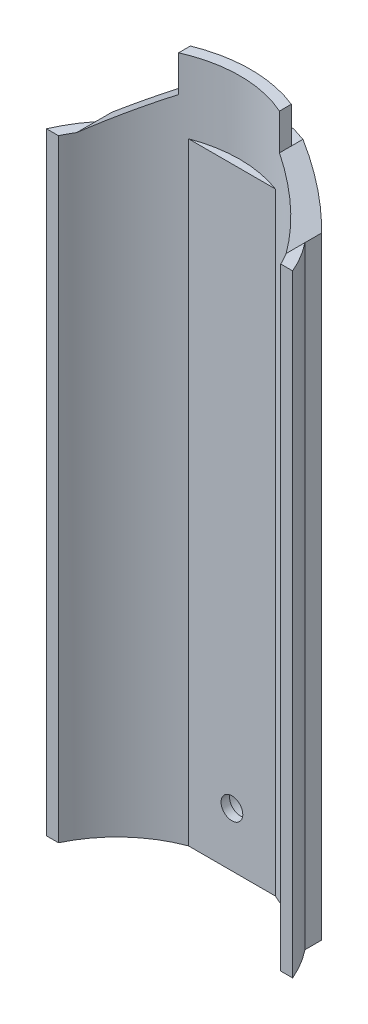
SolidWorks part; units mm, degrees
material "尼龙 6/10"
ref_plane "前视基准面" through (0, 0, 0) normal (0, 0, 1) x (1, 0, 0)
ref_plane "上视基准面" through (0, 0, 0) normal (0, 1, 0) x (1, 0, 0)
ref_plane "右视基准面" through (0, 0, 0) normal (1, 0, 0) x (0, 0, -1)
other "Configuration Table"
sketch "草图1" plane through (0, 0, 0) normal (0, 1, 0) x (1, 0, 0)
  circle A0 centre (0, 0) radius 20
  circle A1 centre (0, 0) radius 17
  dimension "D1" = 40
  dimension "D2" = 34
extrude "凸台-拉伸1" add sketch "草图1" along normal blind 80.6
sketch "草图2" plane through (0, 0, 0) normal (0, 0, 1) x (1, 0, 0)
  line L0 (-14.47, 0) -> (14.47, 0) construction
  line L1 (-20, 0) -> (20, 0) construction
  line L3 (-14.47, 0) -> (-20, 0)
  line L4 (-14.47, 0) -> (-14.47, 80.6)
  line L5 (-14.47, 80.6) -> (-20, 80.6)
  line L6 (-20, 0) -> (-20, 80.6)
  line L7 (14.47, 0) -> (20, 0)
  line L8 (14.47, 0) -> (14.47, 80.6)
  line L9 (14.47, 80.6) -> (20, 80.6)
  line L10 (20, 0) -> (20, 80.6)
  point P6 (0, 0)
  dimension "D1" = 28.94
extrude "切除-拉伸1" cut sketch "草图2" against normal through all
sketch "草图3" plane through (0, 0, 0) normal (0, 0, 1) x (1, 0, 0)
  line L0 (-6.97, 80.6) -> (6.97, 80.6) construction
  line L1 (14.47, 80.6) -> (-14.47, 80.6) construction
  line L3 (-6.97, 80.6) -> (-14.47, 75.6)
  line L8 (-14.47, 0) -> (-14.47, 80.6) construction
  line L10 (6.97, 80.6) -> (14.47, 75.6)
  line L11 (14.47, 80.6) -> (14.47, 0) construction
  line L12 (14.47, 75.6) -> (14.47, 80.6)
  line L13 (14.47, 80.6) -> (6.97, 80.6)
  line L14 (-14.47, 75.6) -> (-14.47, 80.6)
  line L15 (-14.47, 80.6) -> (-6.97, 80.6)
  point P5 (0, 80.6)
  dimension "D1" = 13.94
  dimension "D2" = 5
  dimension "D3" = 7.5
  dimension "D4" = 5
extrude "切除-拉伸2" cut sketch "草图3" against normal through all
sketch "草图4" plane through (0, 0, 0) normal (0, 1, 0) x (1, 0, 0)
  line L0 (0, -1000) -> (0, 49000) construction
  line L1 (-17, 7.2973) -> (-15.3542, 7.2973)
  line L2 (15.3542, 7.2973) -> (17, 7.2973)
  arc A0 (15.3542, 7.2973) -> (-15.3542, 7.2973) centre (0, 0) ccw
  arc A1 (17, 7.2973) -> (-17, 7.2973) centre (0, 0) ccw
  point P9 (0, 7.2973)
  dimension "D1" = 34
  dimension "D2" = 37
  dimension "D3" = 34
extrude "凸台-拉伸3" add sketch "草图4" along normal blind 75.6
sketch "草图5" plane through (0, 0, 0) normal (0, 1, 0) x (1, 0, 0)
  line L0 (0, -1000) -> (0, 49000) construction
  line L1 (-6.97, 17.1368) -> (6.97, 17.1368) construction
  line L2 (6.97, 17.1368) -> (6.97, 15.5055)
  line L3 (-6.97, 17.1368) -> (-6.97, 15.5055)
  arc A0 (6.97, 17.1368) -> (-6.97, 17.1368) centre (0, 0) ccw
  arc A2 (6.97, 15.5055) -> (-6.97, 15.5055) centre (0, 0) ccw
  point P11 (0, 17.1368)
  dimension "D1" = 13.94
extrude "凸台-拉伸5" add sketch "草图5" along normal blind 5 from surface starting at face at (0, 80.6, -17.8129)
sketch "草图6" plane through (0, 0, 0) normal (0, 1, 0) x (1, 0, 0)
  line L4 (14.47, 11.5269) -> (14.47, 13.8065)
  line L5 (15.3542, 7.2973) -> (17, 7.2973)
  line L6 (-17, 7.2973) -> (-15.3542, 7.2973)
  line L7 (-14.47, 13.8065) -> (-14.47, 11.5269)
  line L8 (14.47, 11.5269) -> (14.47, 13.8065)
  line L9 (15.3542, 7.2973) -> (17, 7.2973)
  line L10 (-17, 7.2973) -> (-15.3542, 7.2973)
  line L11 (-14.47, 13.8065) -> (-14.47, 11.5269)
  arc A4 (17, 7.2973) -> (14.47, 11.5269) centre (0, 0) ccw
  arc A5 (15.3542, 7.2973) -> (-15.3542, 7.2973) centre (0, 0) ccw
  arc A6 (-14.47, 11.5269) -> (-17, 7.2973) centre (0, 0) ccw
  arc A7 (14.47, 13.8065) -> (-14.47, 13.8065) centre (0, 0) ccw
  arc A8 (17, 7.2973) -> (14.47, 11.5269) centre (0, 0) ccw
  arc A9 (15.3542, 7.2973) -> (-15.3542, 7.2973) centre (0, 0) ccw
  arc A10 (-14.47, 11.5269) -> (-17, 7.2973) centre (0, 0) ccw
  arc A11 (14.47, 13.8065) -> (-14.47, 13.8065) centre (0, 0) ccw
  dimension "D1" = 0
extrude "凸台-拉伸6" add sketch "草图6" against normal blind 9
sketch "草图7" plane through (0, 0, 0) normal (0, 1, 0) x (1, 0, 0)
  line L0 (0, -1000) -> (0, 49000) construction
  line L1 (-6, 15.906) -> (6, 15.906)
  arc A0 (6, 15.906) -> (-6, 15.906) centre (0, 0) ccw
  point P9 (0, 15.906)
  dimension "D1" = 12
extrude "凸台-拉伸7" add sketch "草图7" along normal up to vertex (75.6 mm away) from surface up to point (-14.47, 75.6, -8.923) starting at face at (0, -9, -11.9902)
sketch "草图8" plane through (0, 0, 0) normal (0, 1, 0) x (1, 0, 0)
  line L0 (6, 15.906) -> (6, 19.0788) construction
  line L1 (6, 19.0788) -> (-6, 19.0788)
  line L2 (-6, 19.0788) -> (-6, 15.906) construction
  arc A0 (14.47, 13.8065) -> (-14.47, 13.8065) centre (0, 0) ccw construction
  arc A1 (6, 19.0788) -> (-6, 19.0788) centre (0, 0) ccw
extrude "切除-拉伸3" cut sketch "草图8" along normal blind 15 from surface starting at face at (0, -9, -11.9845)
sketch "草图9" plane through (0, 0, 0) normal (0, 0, 1) x (1, 0, 0)
  line L0 (-6, -9) -> (6, -9) construction
  line L1 (-6, 6) -> (-6, -9) construction
  circle A0 centre (0, -1.5) radius 1.5
  dimension "D1" = 3
  dimension "D2" = 7.5
  dimension "D3" = 6
extrude "切除-拉伸4" cut sketch "草图9" against normal through all
sketch "草图10" plane through (0, 0, 0) normal (0, 0, 1) x (1, 0, 0)
  circle A0 centre (0, -1.5) radius 2.6
  dimension "D1" = 5.2
extrude "切除-拉伸5" cut sketch "草图10" along normal blind 2 from surface starting at face at (-1.5, -1.5, -19.0788)
sketch "草图11" plane through (0, 0, 0) normal (0, 0, 1) x (1, 0, 0)
  line L0 (6, 6) -> (2, 6)
  line L1 (-6, 6) -> (6, 6) construction
  line L2 (2, 6) -> (6, 1.25)
  line L3 (6, 6) -> (6, -9) construction
  line L4 (6, 1.25) -> (6, 6)
  line L5 (-6, 6) -> (-2, 6)
  line L6 (-6, 6) -> (6, 6) construction
  line L7 (-2, 6) -> (-6, 1.25)
  line L8 (-6, 6) -> (-6, -9) construction
  line L9 (-6, 1.25) -> (-6, 6)
  dimension "D1" = 4.75
  dimension "D2" = 4
  dimension "D3" = 4
  dimension "D4" = 4.75
extrude "凸台-拉伸8" add sketch "草图11" against normal up to surface (0.821 mm away) from surface up to face at (0, 28.8026, -17.3135) starting at face at (-2.6, -1.5, -19.0788)
